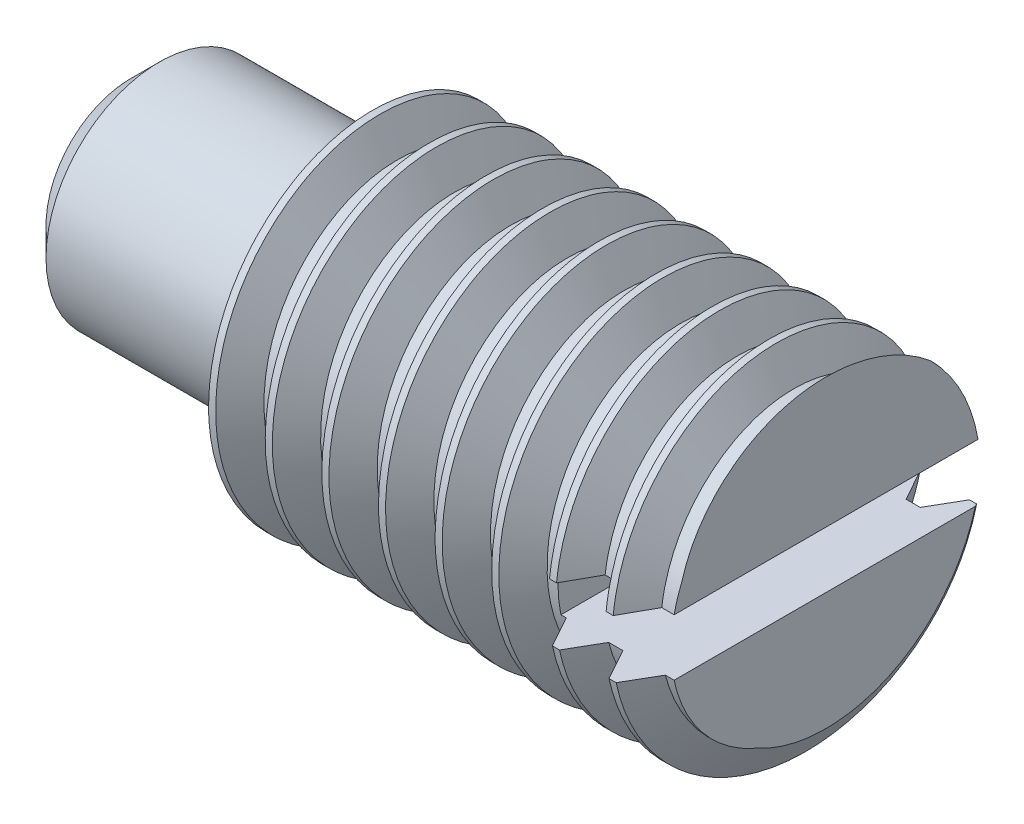
SolidWorks part; units mm, degrees
ref_plane "Front Plane" through (0, 0, 0) normal (0, 0, 1) x (1, 0, 0)
ref_plane "Top Plane" through (0, 0, 0) normal (0, 1, 0) x (1, 0, 0)
ref_plane "Right Plane" through (0, 0, 0) normal (1, 0, 0) x (0, 0, -1)
sketch "Sketch1" plane through (0, 0, 0) normal (0, 0, 1) x (1, 0, 0)
  line L0 (0, 0) -> (12, 0) construction
  line L1 (0, 2) -> (4, 2)
  line L2 (4, 2) -> (4, 3)
  line L3 (4, 3) -> (12, 3)
  line L4 (12, 3) -> (12, 0)
  line L5 (0, 2) -> (0, 0)
  line L6 (0, 0) -> (12, 0)
  dimension "D1" = 12
  dimension "D2" = 4
  dimension "D3" = 4
  dimension "D4" = 6
revolve "Revolve1" add sketch "Sketch1" angle 360 about L0
sketch "Sketch2" plane through (0, 0, 0) normal (0, 0, 1) x (1, 0, 0)
  line L0 (12, -3) -> (12, 3) construction
  line L1 (14, -0.5) -> (10, -0.5)
  line L2 (14, -0.5) -> (14, 0.5)
  line L3 (14, 0.5) -> (10, 0.5)
  line L4 (10, -0.5) -> (10, 0.5)
  line L5 (14, -0.5) -> (10, 0.5) construction
  line L6 (14, 0.5) -> (10, -0.5) construction
  point P0 (12, 0)
  dimension "D1" = 1
  dimension "D2" = 2
extrude "Cut-Extrude1" cut sketch "Sketch2" against normal through all both and the other way through all
thread "Thread1" pitch 1 method cut trim with start face yes trim with end face yes profile "Thread Profile1" start angle 0, offset 1, length 10, pitch 1, diameter 6
ref_plane "Plane1" through (3, 0, -3) normal (0, -1, 0) x (0, 0, -1)
sketch "Thread Profile1" plane through (3, 0, -3) normal (0, -1, 0) x (0, 0, -1)
  line L0 (0, 0) -> (0, 1) construction
  line L11 (0, 0) -> (0, 0.875)
  line L12 (0, 0.875) -> (-0.5413, 0.5625)
  line L13 (-0.5413, 0.5625) -> (-0.5413, 0.3125)
  line L15 (-0.5413, 0.3125) -> (0, 0)
  line L17 (-0.5413, 0.4375) -> (0, 0.4375) construction
  point P2 (0, 0)
  dimension "Pitch" = 1
  dimension "Profile_Angle" = 60
  dimension "Profile_Land" = 0.25
  dimension "Profile_Height" = 0.5413
chamfer "Chamfer1" distance 0.5 angle 45 1 edges at (0, 0, 2)
